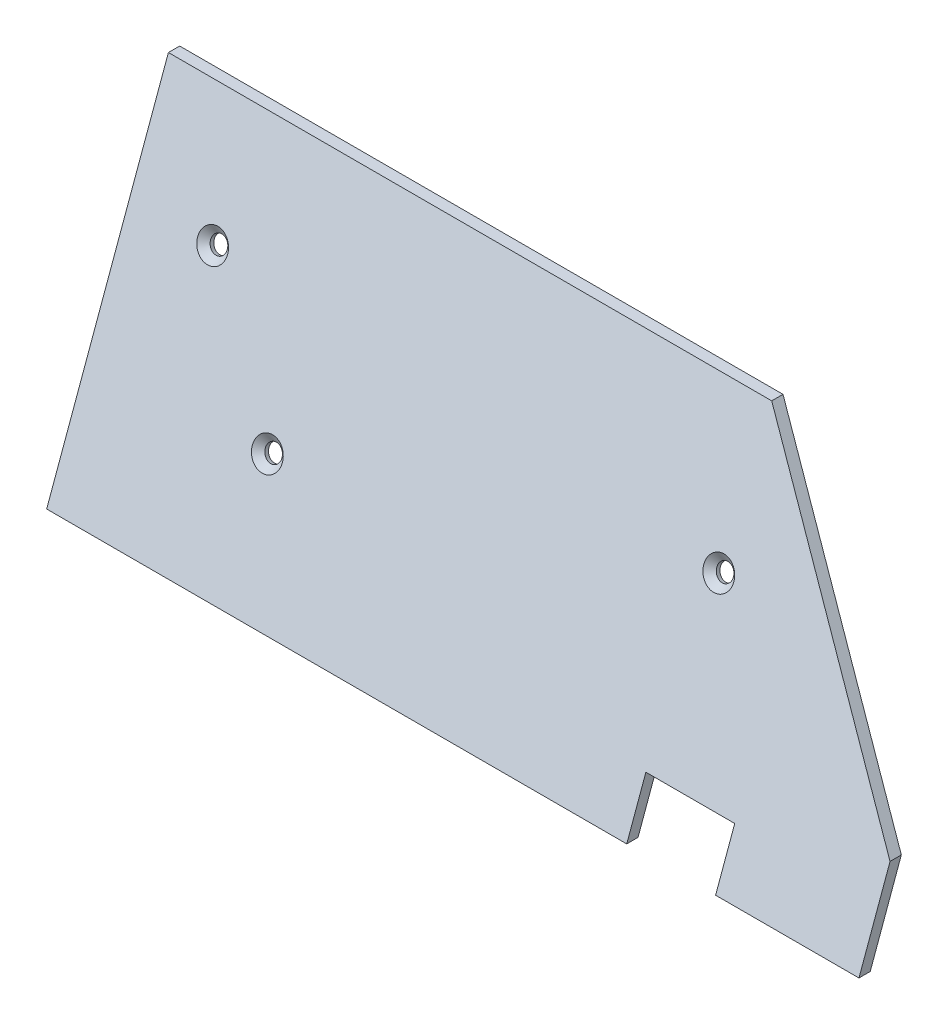
SolidWorks part; units mm, degrees
ref_plane "Front Plane" through (0, 0, 0) normal (0, 0, 1) x (1, 0, 0)
ref_plane "Top Plane" through (0, 0, 0) normal (0, 1, 0) x (1, 0, 0)
ref_plane "Right Plane" through (0, 0, 0) normal (1, 0, 0) x (0, 0, -1)
sketch "Sketch1" plane through (0, 0, 0) normal (1, 0, 0) x (0, 0, -1)
  line L0 (0, 0) -> (-2.3622, 0)
  line L1 (-2.3622, 0) -> (23.1157, 70)
  line L2 (23.1157, 70) -> (25.4779, 70)
  line L3 (25.4779, 70) -> (0, 0)
  dimension "D1" = 2.3622
  dimension "D2" = 2.3622
  dimension "D3" = 70
  dimension "D4" = 70
extrude "Main" add sketch "Sketch1" along normal mid plane 170
hole_wizard "BackBracketHoles" positions "Sketch2" profile "Sketch3" countersink size "M3" standard "ANSI Metric"
sketch "Sketch2" plane through (0, 0.7592, 2.0859) normal (0, 0.342, 0.9397) x (1, 0, 0)
  line L0 (-85, 73.6845) -> (-85, -0.8079) construction
  line L1 (85, -0.8079) -> (-85, -0.8079) construction
  point P0 (-67.6378, 50.0021)
  point P2 (-47.6378, 25.0021)
  dimension "D1" = 17.3622
  dimension "D2" = 50.81
  dimension "D3" = 25.81
  dimension "D4" = 37.3622
sketch "Sketch3" plane through (-67.6378, 47.7458, -15.0158) normal (1, 0, 0) x (0, -0.9397, 0.342)
  line L0 (0, 0) -> (0, 5)
  line L1 (0, 5) -> (1.75, 5)
  line L2 (1.75, 5) -> (1.75, 1.4)
  line L3 (1.75, 1.4) -> (3.15, 0)
  line L5 (3.15, 0) -> (0, 0)
  line L6 (-1.75, 1.4) -> (-3.15, 0) construction
  line L10 (0, 5) -> (-1.75, 5) construction
  line L11 (0, -6.35) -> (0, 107.95) construction
  dimension "Hole Dia." = 3.5
  dimension "Hole Depth" = 5
  dimension "Near C'Sink Dia." = 6.3
  dimension "Near C'Sink Angle" = 90
  dimension "Drill Angle" = 180
sketch "Sketch4" plane through (0, 0, 0) normal (0, 0, 1) x (1, 0, 0)
  line L0 (85, 0) -> (100, 0)
  line L1 (100, 0) -> (41.263, 70)
  line L2 (85, 70) -> (-85, 70) construction
  line L3 (41.263, 70) -> (41.263, 0)
  line L4 (85, 0) -> (-85, 0) construction
  line L5 (41.263, 0) -> (85, 0)
  line L6 (100, 0) -> (100, 70)
  line L7 (100, 70) -> (41.263, 70)
  line L8 (85, 70) -> (85, 0) construction
  dimension "D1" = 50
  dimension "D2" = 15
extrude "Cut-Extrude1" cut sketch "Sketch4" against normal blind 28.6 contours L6 L7 L1 region at (80.421, 46.6667, 0)
hole_wizard "CSK for M3 Flat Head Machine Screw1" positions "Sketch5" profile "Sketch6" countersink size "M3" standard "ANSI Metric"
sketch "Sketch5" plane through (0, 0.7592, 2.0859) normal (0, 0.342, 0.9397) x (1, 0, 0)
  point P0 (40, 45.0021)
sketch "Sketch6" plane through (40, 43.0473, -13.3057) normal (1, 0, 0) x (0, -0.9397, 0.342)
  line L0 (0, 0) -> (0, 5)
  line L1 (0, 5) -> (1.75, 5)
  line L2 (1.75, 5) -> (1.75, 1.4)
  line L3 (1.75, 1.4) -> (3.15, 0)
  line L5 (3.15, 0) -> (0, 0)
  line L6 (-1.75, 1.4) -> (-3.15, 0) construction
  line L10 (0, 5) -> (-1.75, 5) construction
  line L11 (0, -6.35) -> (0, 107.95) construction
  dimension "Hole Dia." = 3.5
  dimension "Hole Depth" = 5
  dimension "Near C'Sink Dia." = 6.3
  dimension "Near C'Sink Angle" = 90
  dimension "Drill Angle" = 180
sketch "Sketch7" plane through (0, 0, 0) normal (0, 0, 1) x (1, 0, 0)
  line L0 (36.4, 11.002) -> (36.4, 0.002) construction
  line L1 (36.4, 11.002) -> (55, 11.002)
  line L2 (36.4, 11.002) -> (36.4, 0.002)
  line L3 (36.4, 0.002) -> (55, 0.002)
  line L4 (55, 11.002) -> (55, 0.002)
  line L6 (36.4, 11.002) -> (55, 11.002) construction
  line L7 (36.4, 0.002) -> (55, 0.002)
  line L8 (36.4, 0.002) -> (36.4, -0.998)
  line L9 (36.4, -0.998) -> (55, -0.998)
  line L10 (55, 0.002) -> (55, -0.998)
  dimension "D1" = 1
extrude "Cut-Extrude3" cut sketch "Sketch7" against normal up to surface (29.6367 mm away) from offset 30 contours L10 L3 L8 L9 | L4 L1 L2 L3 region at (45.7, 5.502, 0) region at (45.7, -0.498, 0) up to face at (40, 40.6437, -14.7931)
